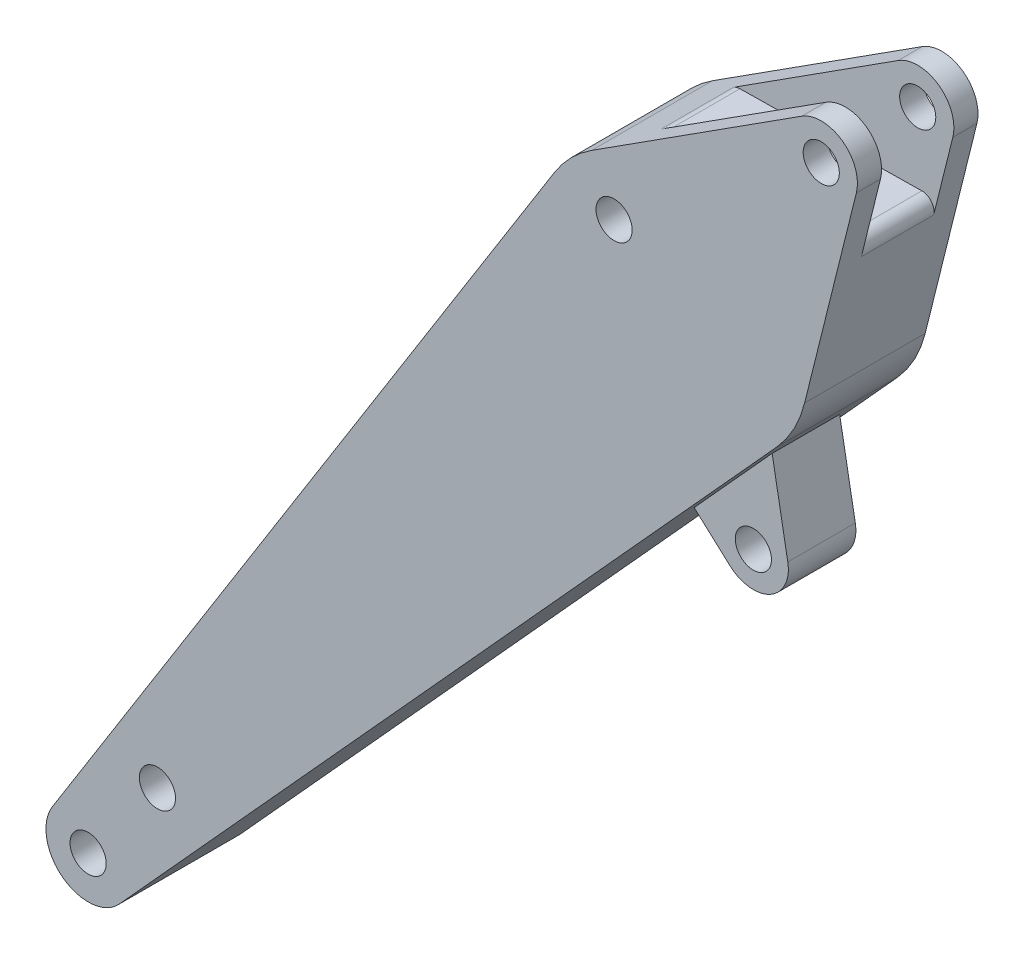
SolidWorks part; units mm, degrees
ref_plane "前视基准面" through (0, 0, 0) normal (0, 0, 1) x (1, 0, 0)
ref_plane "上视基准面" through (0, 0, 0) normal (0, 1, 0) x (1, 0, 0)
ref_plane "右视基准面" through (0, 0, 0) normal (1, 0, 0) x (0, 0, -1)
sketch "草图1" plane through (0, 0, 0) normal (0, 0, 1) x (1, 0, 0)
  line L0 (84.9524, 101.1252) -> (168.9456, 46.856) construction
  line L1 (255.3141, 96.6057) -> (199.0919, 34.648)
  line L2 (255.3141, 96.6057) -> (260.2111, 116.2752)
  line L3 (255.6812, 119.5257) -> (236.3769, 107.1531)
  line L4 (236.3769, 107.1531) -> (193.5351, 38.8599)
  line L5 (257.3, 117) -> (196.5, 37) construction
  line L6 (236.3769, 107.1531) -> (244.8958, 100.6787) construction
  line L7 (255.3141, 96.6057) -> (247.3161, 103.8633) construction
  line L8 (196.5, 37) -> (257.3, 37) construction
  line L9 (257.3, 37) -> (257.3, 117) construction
  arc A0 (193.5351, 38.8599) -> (199.0919, 34.648) centre (196.5, 37) ccw
  arc A1 (255.6812, 119.5257) -> (260.2111, 116.2752) centre (257.3, 117) cw
  circle A4 centre (196.5, 37) radius 1.5
  circle A5 centre (202.2483, 44.5635) radius 1.5
  circle A6 centre (257.3, 117) radius 1.5
  circle A7 centre (240.1188, 104.3092) radius 1.5
  dimension "D2" = 3
  dimension "D3" = 16.5
  dimension "D4" = 3
  dimension "D5" = 3.5
  dimension "D1" = 100
  dimension "D6" = 4
  dimension "D7" = 10.7
  dimension "D8" = 10.8
  dimension "D9" = 80
  dimension "D10" = 9.5
  dimension "D11" = 196.5
  dimension "D12" = 37
  dimension "D13" = 60.8
  dimension "D14" = 6
extrude "凸台-拉伸1" add sketch "草图1" along normal blind 5 and the other way blind 5
sketch "草图2" plane through (0, 0, 0) normal (0, 0, 1) x (1, 0, 0)
  line L0 (242.2703, 110.9303) -> (258.938, 111.1614)
  line L1 (255.6812, 119.5257) -> (236.3769, 107.1531) construction
  line L2 (255.3141, 96.6057) -> (260.2111, 116.2752) construction
  line L7 (199.0919, 34.648) -> (255.3141, 96.6057)
  line L8 (255.3141, 96.6057) -> (260.2111, 116.2752)
  line L9 (255.6812, 119.5257) -> (236.3769, 107.1531)
  line L10 (236.3769, 107.1531) -> (193.5351, 38.8599)
  line L11 (199.0919, 34.648) -> (255.3141, 96.6057)
  line L12 (255.3141, 96.6057) -> (260.2111, 116.2752)
  line L13 (255.6812, 119.5257) -> (236.3769, 107.1531)
  line L14 (236.3769, 107.1531) -> (193.5351, 38.8599)
  circle A0 centre (257.3, 117) radius 1.5 construction
  circle A1 centre (257.3, 117) radius 1.5
  arc A4 (193.5351, 38.8599) -> (199.0919, 34.648) centre (196.5, 37) ccw
  arc A6 (260.2111, 116.2752) -> (255.6812, 119.5257) centre (257.3, 117) ccw
  arc A8 (193.5351, 38.8599) -> (199.0919, 34.648) centre (196.5, 37) ccw
  arc A10 (260.2111, 116.2752) -> (255.6812, 119.5257) centre (257.3, 117) ccw
  dimension "D2" = 7
  dimension "D3" = 15
  dimension "D1" = 0
extrude "切除-拉伸1" cut sketch "草图2" against normal blind 3 and the other way blind 3 contours L12 A10 L13 L0 A1 region at (253.3987, 114.3214, 0)
sketch "草图3" plane through (0, 0, 0) normal (0, 0, 1) x (1, 0, 0)
  line L0 (244.5601, 84.7547) -> (247.5223, 82.0667)
  line L1 (199.0919, 34.648) -> (255.3141, 96.6057) construction
  line L2 (251.0285, 91.8829) -> (252.3246, 84.7315)
  line L3 (244.5601, 84.7547) -> (251.0285, 91.8829)
  circle A0 centre (249.4711, 84.2143) radius 1.5
  arc A1 (247.5223, 82.0667) -> (252.3246, 84.7315) centre (249.4711, 84.2143) ccw
  dimension "D1" = 3
  dimension "D2" = 2.9
  dimension "D3" = 4
extrude "凸台-拉伸4" add sketch "草图3" along normal blind 2.8 and the other way blind 2.8
fillet "圆角1" radius 10 2 edges at (255.3141, 96.6057, 0) (236.3769, 107.1531, 0)
fillet "圆角2" radius 1 2 edges at (258.938, 111.1614, 0) (242.2703, 110.9303, 0)
scale "Scale1" scale about centroid uniform scaling yes scale factor 1.5
